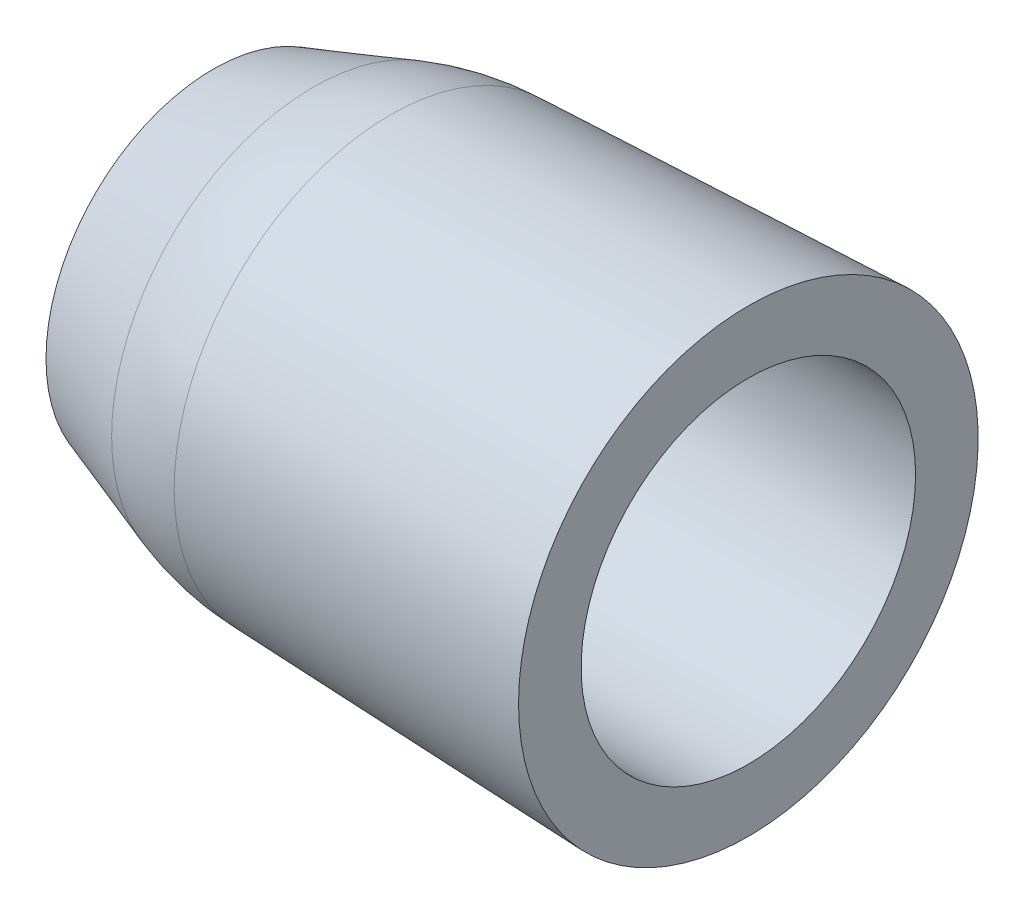
SolidWorks part; units mm, degrees
ref_plane "Front Plane" through (0, 0, 0) normal (0, 0, 1) x (1, 0, 0)
ref_plane "Top Plane" through (0, 0, 0) normal (0, 1, 0) x (1, 0, 0)
ref_plane "Right Plane" through (0, 0, 0) normal (1, 0, 0) x (0, 0, -1)
sketch "Sketch2" plane through (0, 0, 0) normal (0, 0, 1) x (1, 0, 0)
  line L0 (-27.8095, 0) -> (-2.4095, 0) construction
  line L1 (-2.4095, 10.9078) -> (-21.2812, 10.1867)
  line L2 (-21.2812, 10.1867) -> (-27.8095, 7.9375)
  line L3 (-27.8095, 7.9375) -> (-27.8095, 0)
  line L4 (-2.4095, 10.9078) -> (-2.4095, 0)
  line L5 (-27.8095, 0) -> (-2.4095, 0)
  line L6 (-27.8095, 0) -> (-2.4095, 0)
  dimension "D1" = 7.9375
  dimension "D2" = 25.4
revolve "Revolve1" add sketch "Sketch2" angle 360 about L0 region at (-14.6414, 5.1104, 0)
sketch "Sketch3" plane through (-2.4095, 0, 0) normal (1, 0, 0) x (0, 0, -1)
  circle A0 centre (0, 0) radius 7.9375
  dimension "D1" = 15.875
extrude "Cut-Extrude1" cut sketch "Sketch3" against normal blind 25.146
fillet "Fillet1" radius 12.7 1 edges at (-21.2812, 0, 10.1867)
sketch "Sketch4" plane through (-27.5555, 0, 0) normal (1, 0, 0) x (0, 0, -1)
  circle A0 centre (-2.4877, 4.1156) radius 1.1723
extrude "Cut-Extrude2" cut sketch "Sketch4" against normal blind 2.54
